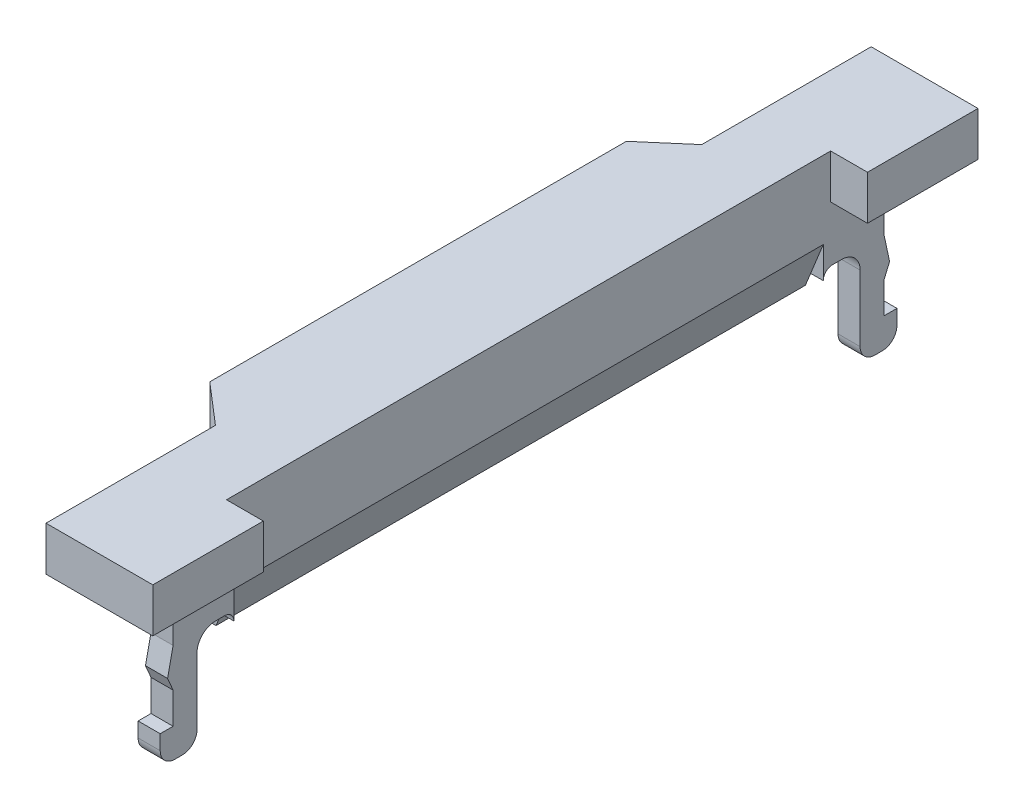
SolidWorks part; units mm, degrees
ref_plane "Plano frontal" through (0, 0, 0) normal (0, 0, 1) x (1, 0, 0)
ref_plane "Plano superior" through (0, 0, 0) normal (0, 1, 0) x (1, 0, 0)
ref_plane "Plano direito" through (0, 0, 0) normal (1, 0, 0) x (0, 0, -1)
sketch "Esboço1" plane through (0, 0, 0) normal (0, 1, 0) x (1, 0, 0)
  line L0 (2, 8.2) -> (2, 11.2)
  line L1 (-0.9, -11.2) -> (2, -11.2)
  line L2 (-2, -5.6547) -> (-2, 5.6547)
  line L3 (-0.9, 11.2) -> (2, 11.2)
  line L4 (2, -11.2) -> (2, -8.2)
  line L5 (-2, -11.2) -> (2, 11.2) construction
  line L6 (-2, 11.2) -> (2, -11.2) construction
  line L7 (2, 8.2) -> (1, 8.2)
  line L8 (-0.9, 11.2) -> (-0.9, 6.6)
  line L9 (2, -8.2) -> (1, -8.2)
  line L10 (1, 8.2) -> (1, -8.2)
  line L11 (-0.9, 6.6) -> (-2, 5.6547)
  line L13 (-2, -5.6547) -> (-0.9, -6.6)
  line L14 (-0.9, -6.6) -> (-0.9, -11.2)
  point P0 (0, 0)
  dimension "D1" = 22.4
  dimension "D2" = 4
  dimension "D3" = 1
  dimension "D4" = 16.4
  dimension "D5" = 8.2
  dimension "D6" = 2.9
  dimension "D7" = 2.9
  dimension "D8" = 13.2
  dimension "D9" = 6.6
extrude "Ressalto-extrusão1" add sketch "Esboço1" along normal blind 1.2
sketch "Esboço2" plane through (0, 0, 0) normal (0, -1, 0) x (1, 0, 0)
  line L0 (1, 8.2) -> (1, -8.2) construction
  line L1 (1, -8) -> (0.4, -8)
  line L2 (1, -8) -> (1, 8)
  line L3 (1, 8) -> (0.4, 8)
  line L4 (0.4, -8) -> (0.4, 8)
  dimension "D1" = 0.6
  dimension "D2" = 8
  dimension "D3" = 16
extrude "Ressalto-extrusão2" add sketch "Esboço2" along normal blind 2.1
chamfer "Chanfro1" distance 1.2 angle 22 1 edges at (1, -2.1, 0) first distance on face at (1, -0.4875, 0.025)
sketch "Esboço3" plane through (0.4, 0, 0) normal (-1, 0, 0) x (0, 0, 1)
  line L0 (-8.25, -1.5) -> (-8.5, -1.5)
  line L1 (-8, -2.1) -> (-8, 0) construction
  line L2 (-9, -2) -> (-9, -3.8)
  line L3 (-9.4, -4.2) -> (-9.6, -4.2)
  line L4 (-10, -3.8) -> (-10, -3.4)
  line L5 (-10, -3.4) -> (-9.65, -3.4)
  line L6 (-11.2, 0) -> (-6.6, 0) construction
  line L7 (-9.65, -3.4) -> (-9.65, -2.55)
  line L8 (-9.65, 0) -> (-8, 0)
  line L9 (-9.65, 0) -> (-9.85, -0.3)
  line L10 (-8, 0) -> (-8, -1.75)
  line L11 (-9.85, -0.3) -> (-9.85, -0.5)
  line L12 (-9.85, -0.5) -> (-9.65, -0.7)
  line L13 (-9.65, -1.5) -> (-9.8, -2.2)
  line L14 (-9.8, -2.2) -> (-9.65, -2.55)
  line L15 (-9.65, -1.5) -> (-9.65, -0.7)
  arc A0 (-8.25, -1.5) -> (-8, -1.75) centre (-8.25, -1.75) cw
  arc A1 (-8.5, -1.5) -> (-9, -2) centre (-8.5, -2) ccw
  arc A2 (-9.6, -4.2) -> (-10, -3.8) centre (-9.6, -3.8) cw
  arc A3 (-9, -3.8) -> (-9.4, -4.2) centre (-9.4, -3.8) cw
  point P17 (-9, -1.5)
  point P20 (-10, -4.2)
  point P23 (-9, -4.2)
  dimension "D1" = 0.25
  dimension "D9" = 0.5
  dimension "D11" = 0.4
  dimension "D2" = 1.5
  dimension "D3" = 2.7
  dimension "D4" = 1
  dimension "D5" = 0.8
  dimension "D6" = 0.35
  dimension "D7" = 0.25
  dimension "D8" = 0.25
  dimension "D10" = 1
  dimension "D12" = 0.3
  dimension "D13" = 0.2
  dimension "D14" = 0.2
  dimension "D15" = 0.2
  dimension "D16" = 1.5
  dimension "D17" = 0.7
  dimension "D18" = 0.15
  dimension "D19" = 0.35
extrude "Ressalto-extrusão3" add sketch "Esboço3" against normal up to surface (0.6 mm away) up to face at (1, -0.0375, 0.025)
mirror "Espelhar1" about plane through (0, 0, 0) normal (0, 0, 1) of "Ressalto-extrusão3"
